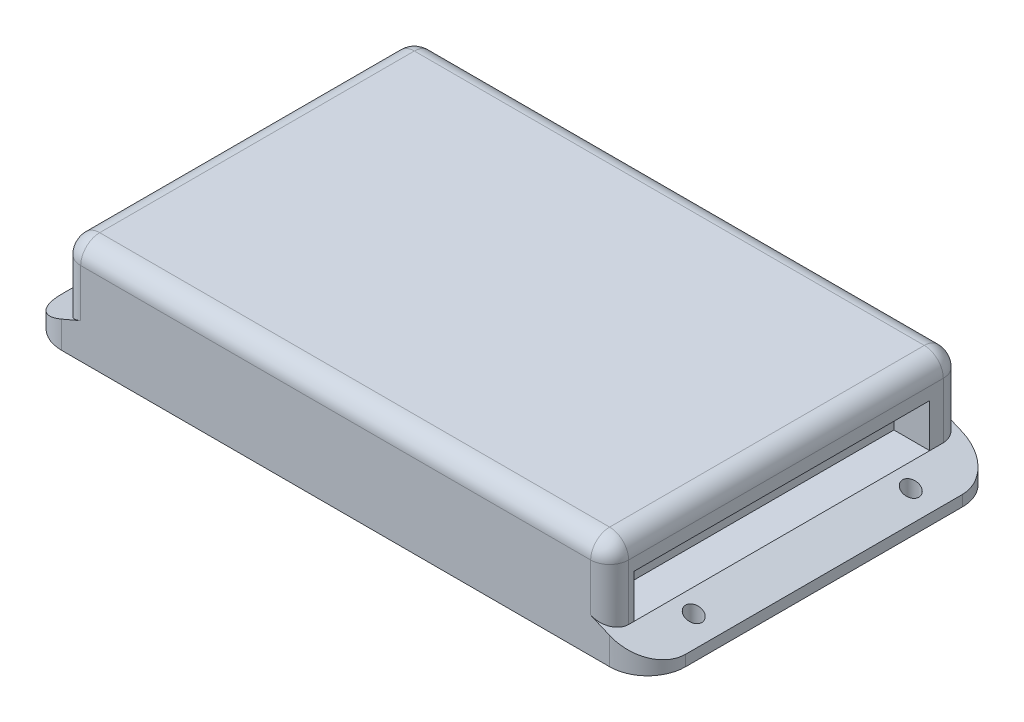
SolidWorks part; units mm, degrees
ref_plane "Front Plane" through (0, 0, 0) normal (0, 0, 1) x (1, 0, 0)
ref_plane "Top Plane" through (0, 0, 0) normal (0, 1, 0) x (1, 0, 0)
ref_plane "Right Plane" through (0, 0, 0) normal (1, 0, 0) x (0, 0, -1)
sketch "Sketch1" plane through (0, 0, 0) normal (0, 1, 0) x (1, 0, 0)
  line L1 (-57.5, -32.5) -> (57.5, -32.5)
  line L2 (-57.5, -32.5) -> (-57.5, 32.5)
  line L3 (-57.5, 32.5) -> (57.5, 32.5)
  line L4 (57.5, -32.5) -> (57.5, 32.5)
  line L5 (-57.5, -32.5) -> (57.5, 32.5) construction
  line L6 (-57.5, 32.5) -> (57.5, -32.5) construction
  point P0 (0, 0)
  dimension "D1" = 65
  dimension "D2" = 115
extrude "Boss-Extrude1" add sketch "Sketch1" along normal blind 5
sketch "Sketch2" plane through (0, 5, 0) normal (0, 1, 0) x (1, 0, 0)
  line L0 (53.5, -20) -> (53.5, 20) construction
  line L1 (0, 0) -> (53.5, 0) construction
  line L2 (57.5, -32.5) -> (57.5, 32.5) construction
  circle A0 centre (53.5, 20) radius 1.5
  circle A1 centre (53.5, -20) radius 1.5
  dimension "D1" = 3
  dimension "D2" = 40
  dimension "D3" = 4
extrude "Cut-Extrude1" cut sketch "Sketch2" against normal through all
mirror "Mirror16" about plane through (0, 0, 0) normal (1, 0, 0) of "Cut-Extrude1"
chamfer "Chamfer1" distance 3 distance2 7 2 edges at (57.5, 5, 0) (-57.5, 5, 0) first distance on face at (57.5, 2.5, 0) first distance on face at (-57.5, 2.5, 0)
fillet "Fillet1" radius 7 4 edges at (57.5, 1, -32.5) (57.5, 1, 32.5) (-57.5, 1, -32.5) (-57.5, 1, 32.5)
sketch "Sketch3" plane through (0, 5, 0) normal (0, 1, 0) x (1, 0, 0)
  line L1 (-50.5, -32.5) -> (50.5, -32.5)
  line L2 (-50.5, -32.5) -> (-50.5, 32.5)
  line L3 (-50.5, 32.5) -> (50.5, 32.5)
  line L4 (50.5, -32.5) -> (50.5, 32.5)
  line L5 (-50.5, -32.5) -> (50.5, 32.5) construction
  line L6 (-50.5, 32.5) -> (50.5, -32.5) construction
  point P0 (0, 0)
extrude "Boss-Extrude2" add sketch "Sketch3" along normal offset from surface (13.8 mm away) 18.8 up to face at (-53.5, 0, -18.5)
fillet "Fillet2" radius 3.5 8 edges at (50.5, 18.8, 0) (0, 18.8, 32.5) (-50.5, 18.8, 0) (0, 18.8, -32.5) (50.5, 11.9, -32.5) (-50.5, 11.9, -32.5) (-50.5, 11.9, 32.5) (50.5, 11.9, 32.5)
sketch "Sketch4" plane through (-50.5, 0, 0) normal (-1, 0, 0) x (0, 0, 1)
  line L0 (-29, 5) -> (29, 5) construction
  line L1 (12.5, 13) -> (-13.5, 13)
  line L2 (12.5, 13) -> (12.5, 5)
  line L3 (12.5, 5) -> (-13.5, 5)
  line L4 (-13.5, 13) -> (-13.5, 5)
  line L5 (12.5, 13) -> (-13.5, 5) construction
  line L6 (12.5, 5) -> (-13.5, 13) construction
  line L7 (-32.5, 6.5) -> (-32.5, 15.3) construction
  point P0 (-0.5, 9)
  dimension "D1" = 19
  dimension "D2" = 26
  dimension "D3" = 8
extrude "Cut-Extrude2" cut sketch "Sketch4" against normal blind 6.6
sketch "Sketch5" plane through (50.5, 0, 0) normal (1, 0, 0) x (0, 0, -1)
  line L0 (-29, 5) -> (29, 5) construction
  line L1 (-28, 13) -> (26.5, 13)
  line L2 (-28, 13) -> (-28, 5)
  line L3 (-28, 5) -> (26.5, 5)
  line L4 (26.5, 13) -> (26.5, 5)
  line L5 (-28, 13) -> (26.5, 5) construction
  line L6 (-28, 5) -> (26.5, 13) construction
  line L7 (-32.5, 6.5) -> (-32.5, 15.3) construction
  point P0 (-0.75, 9)
  point P7 (-23.777, 13.2121)
  dimension "D1" = 4.5
  dimension "D2" = 54.5
  dimension "D3" = 8
extrude "Cut-Extrude3" cut sketch "Sketch5" against normal blind 6.6
